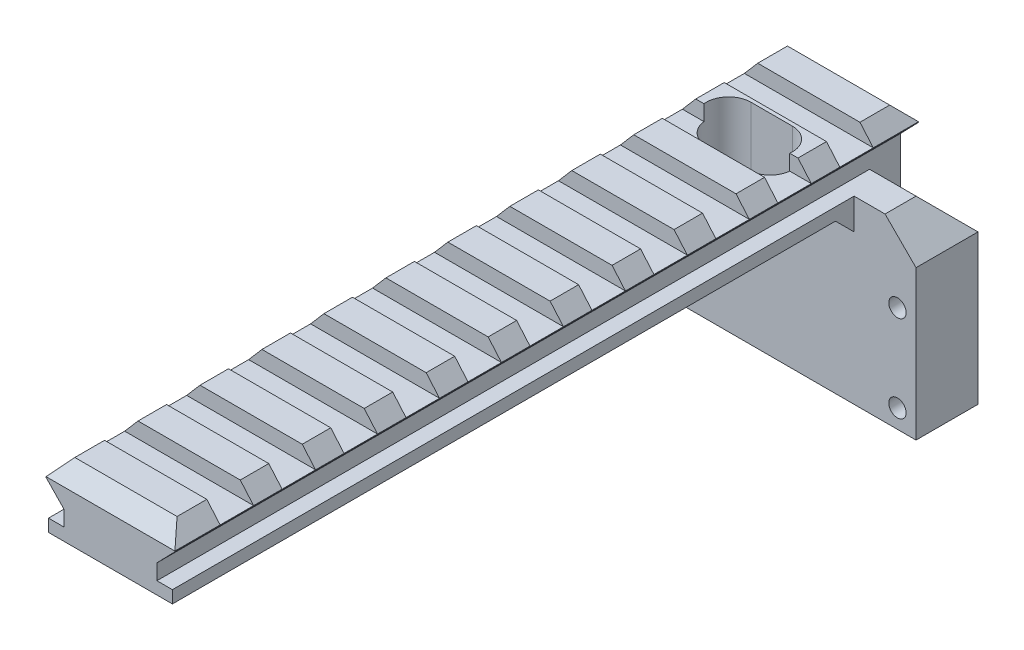
SolidWorks part; units mm, degrees
ref_plane "정면" through (0, 0, 0) normal (0, 0, 1) x (1, 0, 0)
ref_plane "윗면" through (0, 0, 0) normal (0, 1, 0) x (1, 0, 0)
ref_plane "우측면" through (0, 0, 0) normal (1, 0, 0) x (0, 0, -1)
sketch "스케치1" plane through (0, 0, 0) normal (1, 0, 0) x (0, 0, -1)
  line L0 (-10, 27.1) -> (-10, 29.1)
  line L1 (0, 0) -> (-10, 0)
  line L2 (0, 0) -> (0, 29.1)
  line L4 (-10, 0) -> (-10, 27.1)
  line L5 (0, 29.1) -> (-120, 29.1)
  line L7 (-10, 27.1) -> (-120, 27.1)
  line L8 (-120, 29.1) -> (-120, 27.1)
  dimension "D1" = 10
  dimension "D2" = 120
  dimension "D3" = 2
  dimension "D4" = 29.1
extrude "보스-돌출1" add sketch "스케치1" along normal mid plane 40 contours L2 L5 L0 L4 L1 region at (0, 14.55, 5)
sketch "스케치2" plane through (0, 0, 0) normal (0, 0, 1) x (1, 0, 0)
  line L0 (0, 0) -> (0, 44.5769) construction
  line L1 (20, 0) -> (-20, 0) construction
  line L2 (17, 17) -> (17, 3) construction
  circle A0 centre (17, 3) radius 1.4
  circle A1 centre (17, 17) radius 1.4
  circle A2 centre (-17, 3) radius 1.4
  circle A3 centre (-17, 17) radius 1.4
  dimension "D1" = 2.8
  dimension "D2" = 2.8
  dimension "D3" = 3
  dimension "D4" = 14
  dimension "D5" = 17
extrude "컷-돌출1" cut sketch "스케치2" along normal blind 40
extrude "보스-돌출2" add sketch "스케치1<3>" along normal mid plane 20 contours L5 L8 L7 L0 region at (0, 28.1, 65)
sketch "스케치1<3>" plane through (0, 0, 0) normal (1, 0, 0) x (0, 0, -1) same geometry as "스케치1"
sketch "스케치3" plane through (0, 0, 0) normal (0, 0, 1) x (1, 0, 0)
  line L0 (7.5, 29.1) -> (-7.5, 29.1)
  line L1 (10, 29.1) -> (-10, 29.1) construction
  line L2 (-7.5, 29.1) -> (-7.5, 31.6)
  line L3 (-7.5, 31.6) -> (-10.4, 34.6)
  line L4 (-10.4, 34.6) -> (-10.4, 34.7)
  line L5 (-10.4, 34.7) -> (-8.25, 37.2)
  line L6 (-8.25, 37.2) -> (8.25, 37.2)
  line L7 (0, 37.2) -> (0, 29.1) construction
  line L8 (7.5, 29.1) -> (7.5, 31.6)
  line L9 (7.5, 31.6) -> (10.4, 34.6)
  line L10 (10.4, 34.6) -> (10.4, 34.7)
  line L11 (10.4, 34.7) -> (8.25, 37.2)
  dimension "D1" = 16.5
  dimension "D2" = 20.8
  dimension "D3" = 0.1
  dimension "D4" = 3
  dimension "D5" = 2.5
  dimension "D6" = 2.5
  dimension "D7" = 15
extrude "보스-돌출3" add sketch "스케치3" along normal blind 120
sketch "스케치4" plane through (0, 37.2, 0) normal (0, 1, 0) x (1, 0, 0)
  line L0 (-3.3438, -16.8968) -> (3.3438, -16.8968) construction
  line L1 (-3.3438, -13.2968) -> (3.3438, -13.2968)
  line L2 (-3.3438, -20.4968) -> (3.3438, -20.4968)
  line L3 (0, 0) -> (0, -16.8968) construction
  arc A0 (-3.3438, -13.2968) -> (-3.3438, -20.4968) centre (-3.3438, -16.8968) ccw
  arc A1 (3.3438, -20.4968) -> (3.3438, -13.2968) centre (3.3438, -16.8968) ccw
  point P2 (0, -16.8968)
  dimension "D1" = 3.6
extrude "컷-돌출2" cut sketch "스케치4" against normal blind 20
sketch "스케치5" plane through (0, 37.2, 0) normal (0, 1, 0) x (1, 0, 0)
  line L0 (0, 0) -> (0, -10) construction
  line L1 (-12.5, -7.3) -> (12.5, -7.3)
  line L2 (-12.5, -7.3) -> (-12.5, -12.7)
  line L3 (-12.5, -12.7) -> (12.5, -12.7)
  line L4 (12.5, -7.3) -> (12.5, -12.7)
  line L5 (-12.5, -7.3) -> (12.5, -12.7) construction
  line L6 (-12.5, -12.7) -> (12.5, -7.3) construction
  line L7 (8.25, 0) -> (-8.25, 0) construction
  point P0 (0, -10)
  dimension "D1" = 5.4
  dimension "D2" = 25
  dimension "D3" = 7.3
extrude "컷-돌출3" cut sketch "스케치5" against normal blind 2.5
pattern_linear "선형 패턴1" count 11 spacing 10 along (0, 0, 1) of "컷-돌출3"
chamfer "모따기1" distance 3 angle 45 1 edges at (0, 27.1, 10)
sketch "스케치6" plane through (0, 0, 0) normal (0, 0, -1) x (-1, 0, 0)
  circle A0 centre (-17, 3) radius 2.9
  circle A1 centre (-17, 17) radius 2.9
  circle A2 centre (17, 17) radius 2.9
  circle A3 centre (17, 3) radius 2.9
  dimension "D1" = 5.8
  dimension "D2" = 5.8
  dimension "D3" = 5.8
  dimension "D4" = 5.8
extrude "컷-돌출4" cut sketch "스케치6" against normal blind 2
chamfer "모따기2" distance 2 distance2 1.6 4 edges at (14.1, 3, 2) (-19.9, 3, 2) (-19.9, 17, 2) (14.1, 17, 2) first distance on face at (14.1, 3, 2) first distance on face at (-19.9, 3, 2) first distance on face at (-19.9, 17, 2) first distance on face at (14.1, 17, 2)
chamfer "모따기3" distance 2.5 angle 45 2 edges at (0, 37.2, 120) (0, 37.2, 0)
chamfer "모따기4" distance 5 angle 45 3 edges at (20, 29.1, 5) (-20, 29.1, 5)
